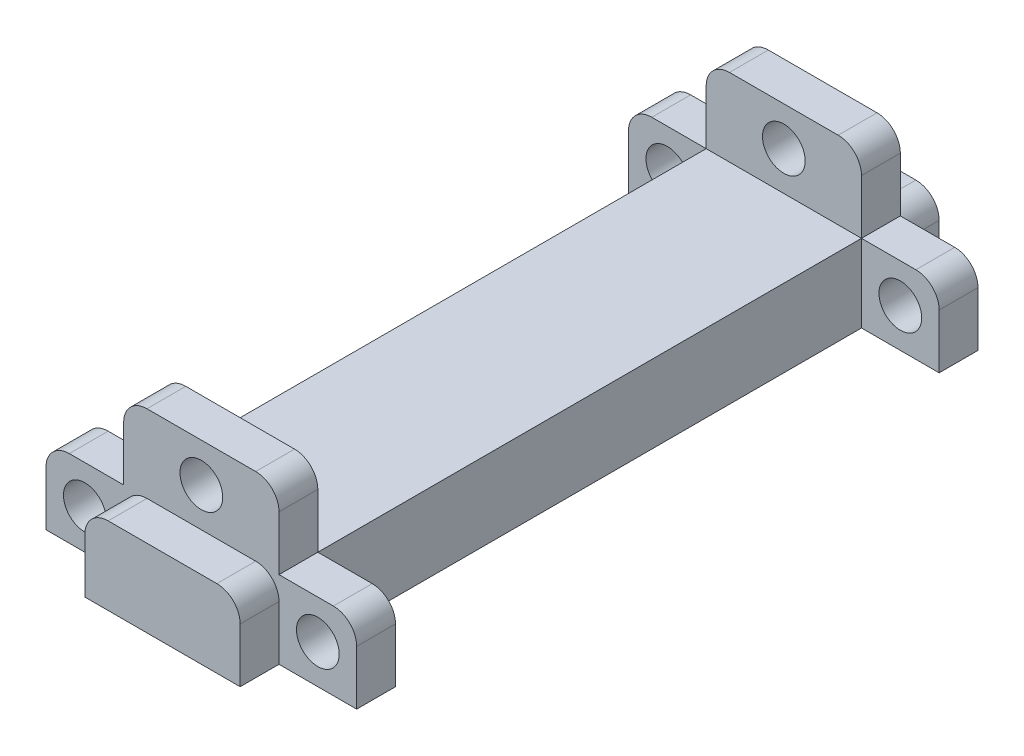
SolidWorks part; units mm, degrees
material "6061 合金"
ref_plane "前视基准面" through (0, 0, 0) normal (0, 0, 1) x (1, 0, 0)
ref_plane "上视基准面" through (0, 0, 0) normal (0, 1, 0) x (1, 0, 0)
ref_plane "右视基准面" through (0, 0, 0) normal (1, 0, 0) x (0, 0, -1)
other "Configuration Table"
sketch "草图1" plane through (0, 0, 0) normal (0, 0, 1) x (1, 0, 0)
  line L1 (0, 0) -> (20, 0)
  line L2 (0, 0) -> (0, 10)
  line L3 (0, 10) -> (20, 10)
  line L4 (20, 0) -> (20, 10)
  dimension "D1" = 20
  dimension "D2" = 10
extrude "凸台-拉伸1" add sketch "草图1" along normal blind 90 contours L2 L3 L4 L1
sketch "草图2" plane through (0, 0, 0) normal (0, 0, -1) x (-1, 0, 0)
  line L1 (-20, 10) -> (0, 10)
  line L2 (-20, 10) -> (-20, 20)
  line L3 (-20, 20) -> (0, 20)
  line L4 (0, 10) -> (0, 20)
  line L5 (0, 0) -> (10, 0)
  line L6 (0, 0) -> (0, 10)
  line L7 (0, 10) -> (10, 10)
  line L8 (10, 0) -> (10, 10)
  line L9 (-20, 0) -> (-30, 0)
  line L10 (-20, 0) -> (-20, 10)
  line L11 (-20, 10) -> (-30, 10)
  line L12 (-30, 0) -> (-30, 10)
  line M12 (0, 10) -> (-20, 10)
  line M13 (-20, 10) -> (-20, 0)
  dimension "D1" = 10
  dimension "D2" = 10
ref_plane "基准面1" through (0, 0, 45) normal (0, 0, -1) x (-1, 0, 0)
extrude "凸台-拉伸2" add sketch "草图2" against normal blind 5 from offset 5 contours L12 L9 L11 M13 | L4 L3 L2 M12 | L6 L5 L8 L7 offset against normal yes
mirror "镜向1" about plane through (0, 0, 45) normal (0, 0, -1) of "凸台-拉伸2"
sketch "草图3" plane through (0, 0, 5) normal (0, 0, -1) x (-1, 0, 0)
  line L1 (-33.8025, 5) -> (20.2955, 5) construction
  line L2 (5, 14.7529) -> (5, -4.7529) construction
  line L3 (-25.6975, 15) -> (5.2513, 15) construction
  line L4 (-10, 22.4765) -> (-10, 13.0669) construction
  line L5 (0, 10) -> (0, 20) construction
  line L6 (-20, 10) -> (-20, 20) construction
  line L7 (-20, 20) -> (0, 20) construction
  line L8 (0, 10) -> (-20, 10) construction
  line L9 (0, 10) -> (10, 10) construction
  line L10 (0, 0) -> (10, 0) construction
  line L11 (10, 0) -> (10, 10) construction
  line L12 (0, 0) -> (0, 10) construction
  line L13 (-25, 12.0122) -> (-25, -3.7537) construction
  line L14 (-20, 0) -> (-20, 10) construction
  line L15 (-30, 0) -> (-30, 10) construction
  circle A0 centre (5, 5) radius 2.75
  circle A1 centre (-10, 15) radius 2.75
  circle A2 centre (-25, 5) radius 2.75
  dimension "D1" = 5.5
extrude "切除-拉伸1" cut sketch "草图3" against normal through all both and the other way through all
fillet "圆角1" radius 3 12 edges at (0, 10, 2.5) (20, 10, 2.5) (20, 20, 7.5) (0, 20, 7.5) (-10, 10, 7.5) (30, 10, 7.5) (30, 10, 82.5) (0, 20, 82.5) (20, 20, 82.5) (-10, 10, 82.5) (0, 10, 87.5) (20, 10, 87.5)
